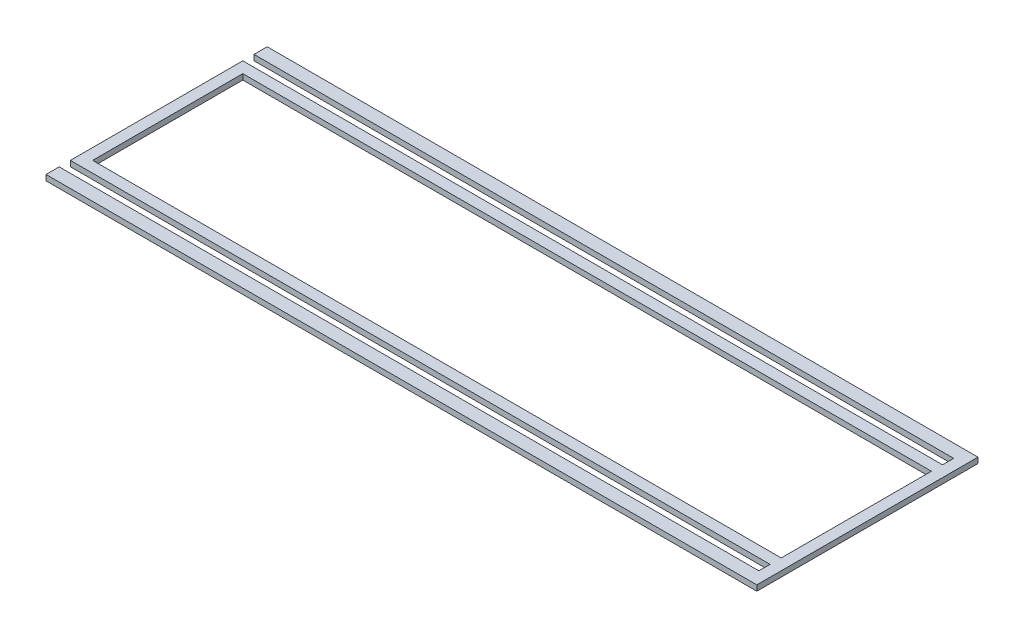
SolidWorks part; units mm, degrees
ref_plane "Front Plane" through (0, 0, 0) normal (0, 0, 1) x (1, 0, 0)
ref_plane "Top Plane" through (0, 0, 0) normal (0, 1, 0) x (1, 0, 0)
ref_plane "Right Plane" through (0, 0, 0) normal (1, 0, 0) x (0, 0, -1)
sketch "Sketch1" plane through (0, 0, 0) normal (0, 1, 0) x (1, 0, 0)
  line L0 (-203.2, 49.2855) -> (-203.2, -49.2855)
  line L1 (-203.2, 63.227) -> (203.2, 63.227)
  line L2 (-203.2, 63.227) -> (-203.2, 55.6863)
  line L3 (-203.2, -63.2269) -> (203.2, -63.2269)
  line L4 (203.2, 63.227) -> (203.2, -63.2269)
  line L5 (-203.2, 63.227) -> (203.2, -63.2269) construction
  line L6 (-203.2, -63.2269) -> (203.2, 63.227) construction
  line L7 (-203.2, -63.2269) -> (190.5, -63.2269)
  line L8 (-203.2, -63.2269) -> (-203.2, -55.6863)
  line L9 (-203.2, -55.6863) -> (196.85, -55.6863)
  line L11 (-203.2, 63.227) -> (190.5, 63.227)
  line L12 (-203.2, 63.227) -> (-203.2, 55.6863)
  line L13 (-203.2, 55.6863) -> (196.85, 55.6863)
  line L15 (-203.2, -55.6863) -> (196.85, -55.6863)
  line L17 (-203.2, -49.2855) -> (196.85, -49.2855)
  line L18 (196.85, -55.6863) -> (196.85, -49.2855)
  line L19 (-203.2, 55.6863) -> (196.85, 55.6863)
  line L21 (-203.2, 49.2855) -> (196.85, 49.2855)
  line L22 (196.85, 55.6863) -> (196.85, 49.2855)
  line L23 (-203.2, -55.6863) -> (-203.2, -63.2269)
  line L25 (-196.85, -42.9355) -> (196.85, -42.9355)
  line L26 (-196.85, -42.9355) -> (-196.85, 42.9355)
  line L27 (-196.85, 42.9355) -> (196.85, 42.9355)
  line L28 (196.85, -42.9355) -> (196.85, 42.9355)
  line L29 (-196.85, -42.9355) -> (196.85, 42.9355) construction
  line L30 (-196.85, 42.9355) -> (196.85, -42.9355) construction
  point P0 (0, 0)
  point P16 (0, 0)
  dimension "D1" = 406.4
  dimension "D4" = 7.5406
  dimension "D5" = 7.5406
  dimension "D6" = 6.4008
  dimension "D7" = 6.4008
  dimension "D3" = 6.35
  dimension "D8" = 6.35
  dimension "D9" = 6.35
  dimension "D10" = 6.35
extrude "Boss-Extrude1" add sketch "Sketch1" along normal mid plane 3.175 contours L1 L13 L2 L9 L3 L4 region at (-3.175, 0, -45.0293)
equation "\"D2@Sketch1\"     = 5.698in - ( 2 * ( 2 * 0.125in))- 4*3/64-(0.008*4)"
equation "\"D1@Sketch1\"=16.00in"
equation "\"D6@Sketch1\"=0.252"
